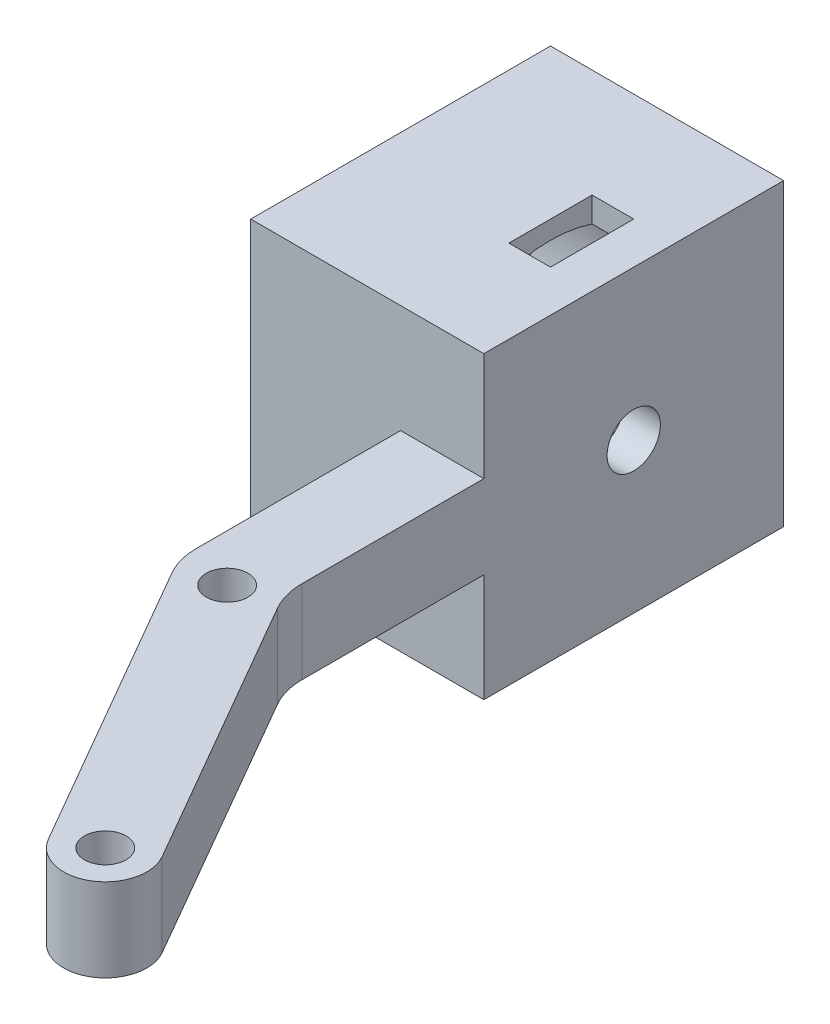
SolidWorks part; units mm, degrees
material "PLA"
ref_plane "Front Plane" through (0, 0, 0) normal (0, 0, 1) x (1, 0, 0)
ref_plane "Top Plane" through (0, 0, 0) normal (0, 1, 0) x (1, 0, 0)
ref_plane "Right Plane" through (0, 0, 0) normal (1, 0, 0) x (0, 0, -1)
sketch "Sketch1" plane through (0, 0, 0) normal (0, 1, 0) x (1, 0, 0)
  line L0 (-6.35, -14.4015) -> (-6.35, 2.54)
  line L1 (0, -12.7) -> (0, 25.4)
  line L2 (0, 25.4) -> (-17.78, 25.4)
  line L3 (-17.78, 25.4) -> (-17.78, 2.54)
  line L4 (-17.78, 2.54) -> (-6.35, 2.54)
  line L5 (0, -12.7) -> (12.7, -34.697)
  line L6 (-6.35, -14.4015) -> (7.2007, -37.872)
  line L7 (0, -12.7) -> (-5.4993, -15.875) construction
  arc A0 (7.2007, -37.872) -> (12.7, -34.697) centre (9.9504, -36.2845) ccw
  circle A1 centre (9.9504, -36.2845) radius 1.5875
  circle A2 centre (-2.7496, -14.2875) radius 1.5875
  dimension "D1" = 3.175
  dimension "D2" = 3.175
  dimension "D6" = 3.175
  dimension "D3" = 150
  dimension "D4" = 6.35
  dimension "D8" = 25.4
  dimension "D10" = 17.78
  dimension "D11" = 38.1
  dimension "D12" = 22.86
  dimension "D13" = 12.7
extrude "Boss-Extrude1" add sketch "Sketch1" along normal blind 22.86
sketch "Sketch2" plane through (0, 22.86, 0) normal (0, 1, 0) x (1, 0, 0)
  line L1 (-6.35, -14.4015) -> (8.7882, -40.6217)
  line L2 (0, -12.7) -> (14.2875, -37.4467)
  line L3 (14.2875, -37.4467) -> (8.7882, -40.6217)
  line L4 (-6.35, -14.4015) -> (7.2007, -37.872) construction
  line L5 (12.7, -34.697) -> (0, -12.7) construction
  line L6 (-6.35, 2.54) -> (0, 2.54)
  line L7 (0, -12.7) -> (0, 25.4) construction
  line L8 (0, 2.54) -> (0, -12.7)
  line L9 (-6.35, -14.4015) -> (-6.35, 2.54)
  arc A0 (7.2007, -37.872) -> (12.7, -34.697) centre (9.9504, -36.2845) ccw construction
extrude "Top Cut" cut sketch "Sketch2" against normal blind 8.255
sketch "Sketch4" plane through (0, 0, 0) normal (0, -1, 0) x (1, 0, 0)
  line L0 (-6.35, -2.54) -> (-6.35, 14.4015)
  line L1 (-6.35, 14.4015) -> (7.2007, 37.872) construction
  line L2 (-6.35, -2.54) -> (-6.35, 14.4015) construction
  line L3 (-6.35, 14.4015) -> (8.7882, 40.6217)
  line L4 (8.7882, 40.6217) -> (14.2875, 37.4467)
  line L5 (-6.35, -2.54) -> (0, -2.54)
  line L7 (0, -2.54) -> (0, 12.7)
  line L8 (0, 12.7) -> (14.2875, 37.4467)
  line L9 (12.7, 34.697) -> (0, 12.7) construction
  arc A0 (12.7, 34.697) -> (7.2007, 37.872) centre (9.9504, 36.2845) ccw construction
extrude "Bottom Cut" cut sketch "Sketch4" against normal blind 8.255
sketch "Sketch3" plane through (0, 22.86, 0) normal (0, 1, 0) x (1, 0, 0)
  line L0 (-17.78, 25.4) -> (-19.05, 24.13)
  line L1 (-19.05, 24.13) -> (-17.78, 22.86)
  line L2 (-17.78, 25.4) -> (-17.78, 2.54) construction
  line L12 (-17.78, 25.4) -> (0, 25.4)
  line L13 (0, 25.4) -> (0, 0)
  line L14 (0, 2.54) -> (0, 25.4) construction
  line L16 (-19.05, 21.59) -> (-17.78, 20.32)
  line L17 (-17.78, 22.86) -> (-19.05, 21.59)
  line L18 (-19.05, 19.05) -> (-17.78, 17.78)
  line L19 (-17.78, 20.32) -> (-19.05, 19.05)
  line L20 (-19.05, 16.51) -> (-17.78, 15.24)
  line L21 (-17.78, 17.78) -> (-19.05, 16.51)
  line L22 (-19.05, 13.97) -> (-17.78, 12.7)
  line L23 (-17.78, 15.24) -> (-19.05, 13.97)
  line L24 (-19.05, 11.43) -> (-17.78, 10.16)
  line L25 (-17.78, 12.7) -> (-19.05, 11.43)
  line L26 (-19.05, 8.89) -> (-17.78, 7.62)
  line L27 (-17.78, 10.16) -> (-19.05, 8.89)
  line L28 (-19.05, 6.35) -> (-17.78, 5.08)
  line L29 (-17.78, 7.62) -> (-19.05, 6.35)
  line L30 (-19.05, 3.81) -> (-17.78, 2.54)
  line L31 (-17.78, 5.08) -> (-19.05, 3.81)
  line L32 (-19.05, 1.27) -> (-17.78, 0)
  line L33 (-17.78, 2.54) -> (-19.05, 1.27)
  line L34 (-17.78, 0) -> (0, 0)
  dimension "D1" = 2.54
  dimension "D2" = 135
  dimension "D3" = 10
extrude "Boss-Extrude2" [suppressed] add sketch "Sketch3" against normal up to surface (5.08 mm away) contours L13 L34 L32 L33 L30 L31 L28 L29 L26 L27 L24 L25 L22 L23 L20 L21 L18 L19 L16 L17 L1 L0 L12 up to face at (-8.89, 0, -13.97)
sketch "Sketch5" plane through (-17.78, 0, 0) normal (-1, 0, 0) x (0, 0, 1)
  line L1 (-25.4, 0) -> (-2.54, 0)
  line L2 (-25.4, 0) -> (-25.4, 22.86)
  line L3 (-25.4, 22.86) -> (-2.54, 22.86)
  line L4 (-2.54, 0) -> (-2.54, 22.86)
  line L5 (-25.4, 0) -> (-2.54, 22.86) construction
  line L6 (-25.4, 22.86) -> (-2.54, 0) construction
  circle A0 centre (-13.97, 11.43) radius 10.033
  point P0 (-13.97, 11.43)
  dimension "D1" = 20.066
extrude "Cut-Extrude1" cut sketch "Sketch5" against normal blind 14.986 contours A0 region at (-17.78, 11.43, -13.97)
sketch "Sketch7" plane through (0, 0, 0) normal (1, 0, 0) x (0, 0, -1)
  line L0 (2.54, 22.86) -> (25.4, 22.86) construction
  line L1 (2.54, 0) -> (25.4, 0)
  line L2 (2.54, 0) -> (2.54, 22.86)
  line L3 (2.54, 22.86) -> (25.4, 22.86)
  line L4 (25.4, 0) -> (25.4, 22.86)
  line L5 (2.54, 0) -> (25.4, 22.86) construction
  line L6 (2.54, 22.86) -> (25.4, 0) construction
  line L7 (25.4, 22.86) -> (25.4, 0) construction
  line L9 (2.54, 0) -> (25.4, 0) construction
  circle A0 centre (13.97, 11.43) radius 2.032
  point P0 (13.97, 11.43)
  dimension "D1" = 4.064
extrude "Cut-Extrude2" cut sketch "Sketch7" against normal through all contours A0 region at (0, 11.43, -13.97)
sketch "Sketch8" plane through (0, 22.86, 0) normal (0, 1, 0) x (1, 0, 0)
  line L0 (0, 2.54) -> (0, 25.4) construction
  line L1 (-6.35, 10.795) -> (-3.175, 10.795)
  line L2 (-6.35, 10.795) -> (-6.35, 17.145)
  line L3 (-6.35, 17.145) -> (-3.175, 17.145)
  line L4 (-3.175, 10.795) -> (-3.175, 17.145)
  line L5 (-6.35, 10.795) -> (-3.175, 17.145) construction
  line L6 (-6.35, 17.145) -> (-3.175, 10.795) construction
  line L7 (-17.78, 25.4) -> (-17.78, 2.54) construction
  line L11 (-17.78, 24.003) -> (-17.78, 3.937) construction
  point P0 (-4.7625, 13.97)
  point P12 (-17.78, 13.97)
  dimension "D1" = 3.175
  dimension "D2" = 6.35
  dimension "D3" = 3.175
extrude "Cut-Extrude3" cut sketch "Sketch8" against normal up to surface (1.9126 mm away) up to face at (-2.794, 11.43, -3.937)
sketch "Sketch9" [suppressed] plane through (0, 0, 0) normal (0, -1, 0) x (1, 0, 0)
  line L0 (0, -2.54) -> (0, -25.4) construction
  line L1 (-6.35, -17.145) -> (-3.175, -17.145)
  line L2 (-6.35, -17.145) -> (-6.35, -10.795)
  line L3 (-6.35, -10.795) -> (-3.175, -10.795)
  line L4 (-3.175, -17.145) -> (-3.175, -10.795)
  line L5 (-6.35, -17.145) -> (-3.175, -10.795) construction
  line L6 (-6.35, -10.795) -> (-3.175, -17.145) construction
  line L7 (-17.78, -2.54) -> (-17.78, -25.4) construction
  point P0 (-4.7625, -13.97)
  point P11 (-17.78, -13.97)
  dimension "D1" = 3.175
  dimension "D2" = 6.35
  dimension "D3" = 3.175
extrude "Cut-Extrude4" [suppressed] cut sketch "Sketch9" against normal up to next
fillet "Fillet1" radius 5.08 2 edges at (0, 11.43, 12.7) (-6.35, 11.43, 14.4015)
